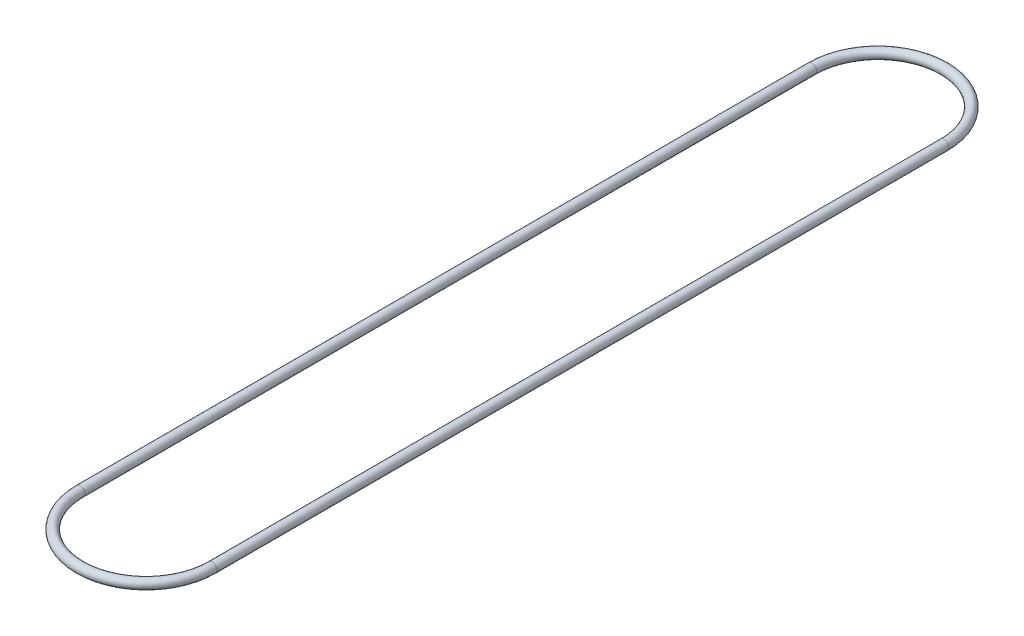
SolidWorks part; units mm, degrees
material "Pure Gold"
ref_plane "Front Plane" through (0, 0, 0) normal (0, 0, 1) x (1, 0, 0)
ref_plane "Top Plane" through (0, 0, 0) normal (0, 1, 0) x (1, 0, 0)
ref_plane "Right Plane" through (0, 0, 0) normal (1, 0, 0) x (0, 0, -1)
ref_plane "Plane1" through (0, 2.5, 0) normal (0, -1, 0) x (0, 0, -1)
sketch "Sketch1" plane through (0, 2.5, 0) normal (0, -1, 0) x (0, 0, -1)
  line L0 (-1.5473, -0.275) -> (1.5, -0.275)
  line L1 (1.5, 0.275) -> (-1.5473, 0.275)
  line L3 (0, 55) -> (0, -55) construction
  arc A1 (1.5, -0.275) -> (1.5, 0.275) centre (1.5, 0) ccw
  arc A2 (-1.5473, 0.275) -> (-1.5473, -0.275) centre (-1.5473, 0) ccw
  dimension "D1" = 1.5
  dimension "D2" = 0.275
ref_plane "Plane2" through (0.2709, 2.5, -1.5473) normal (0.1719, 0, 0.9851) x (-0.9851, 0, 0.1719)
sketch "Sketch2" plane through (0.2709, 2.5, -1.5473) normal (0.1719, 0, 0.9851) x (-0.9851, 0, 0.1719)
  circle A0 centre (0, 0) radius 0.02
  dimension "D1" = 0.04
sweep "Sweep1" add profiles "Sketch2" path "Sketch1"
ref_axis "Axis1" through (0, 2.522, 0) along (0, -1, 0)
pattern_linear "LPattern20" [suppressed] count 60 spacing 0.2 along (0, 1, 0) of bodies 101
